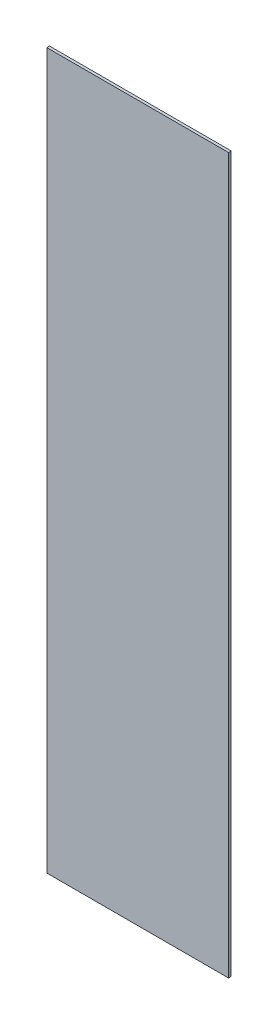
SolidWorks part; units mm, degrees
material "1060 Alloy"
ref_plane "Front Plane" through (0, 0, 0) normal (0, 0, 1) x (1, 0, 0)
ref_plane "Top Plane" through (0, 0, 0) normal (0, 1, 0) x (1, 0, 0)
ref_plane "Right Plane" through (0, 0, 0) normal (1, 0, 0) x (0, 0, -1)
sketch "Sketch1" plane through (0, 0, 0) normal (0, 0, 1) x (1, 0, 0)
  line L1 (-77.5, 304.8) -> (77.5, 304.8)
  line L2 (-77.5, 304.8) -> (-77.5, -304.8)
  line L3 (-77.5, -304.8) -> (77.5, -304.8)
  line L4 (77.5, 304.8) -> (77.5, -304.8)
  line L5 (-77.5, 304.8) -> (77.5, -304.8) construction
  line L6 (-77.5, -304.8) -> (77.5, 304.8) construction
  point P0 (0, 0)
  dimension "D1" = 609.6
  dimension "D2" = 155
extrude "Boss-Extrude1" add sketch "Sketch1" along normal blind 2.305
